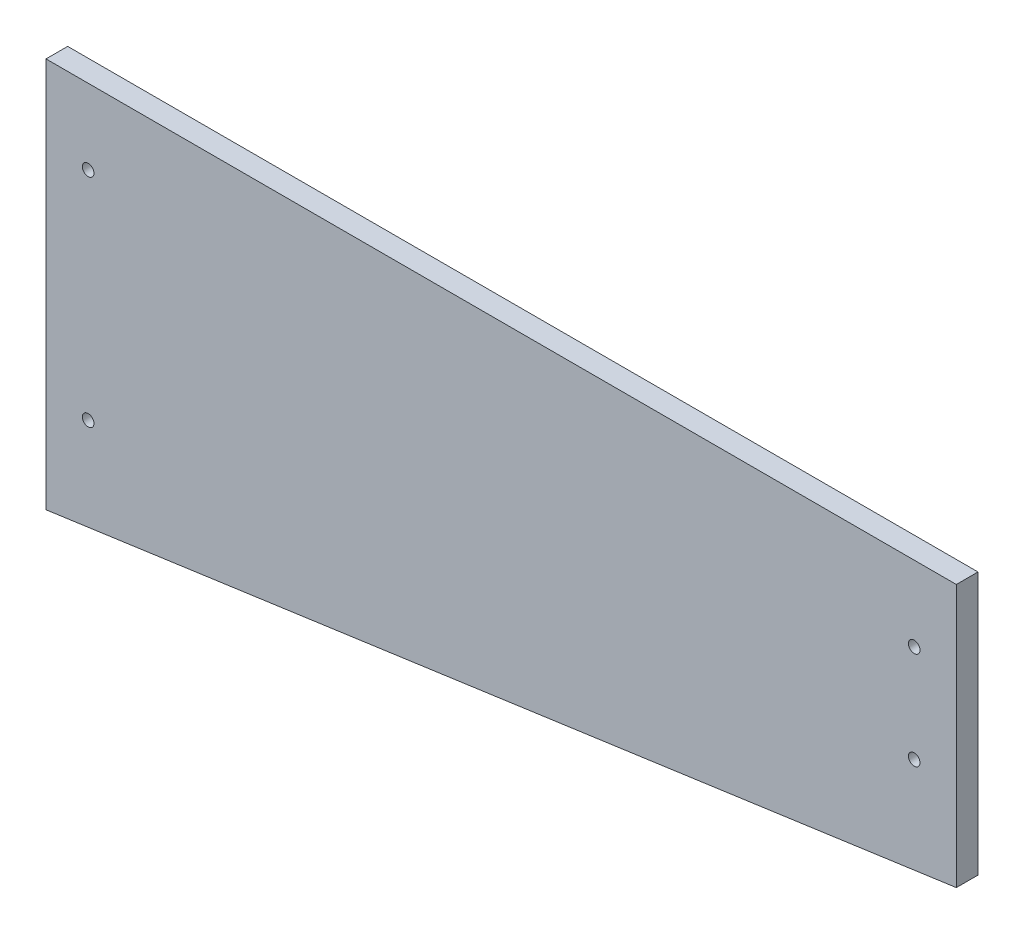
SolidWorks part; units mm, degrees
material "Acrylic (Medium-high impact)"
ref_plane "Front Plane" through (0, 0, 0) normal (0, 0, 1) x (1, 0, 0)
ref_plane "Top Plane" through (0, 0, 0) normal (0, 1, 0) x (1, 0, 0)
ref_plane "Right Plane" through (0, 0, 0) normal (1, 0, 0) x (0, 0, -1)
sketch "Sketch1" plane through (0, 0, 0) normal (0, 0, 1) x (1, 0, 0)
  line L1 (266.7, 114.4016) -> (0, 114.4016)
  line L2 (266.7, 114.4016) -> (266.7, 0)
  line L3 (266.7, 0) -> (0, 0)
  line L4 (0, 114.4016) -> (0, 0)
  line L5 (266.7, 114.4016) -> (0, 0) construction
  line L6 (266.7, 0) -> (0, 114.4016) construction
  point P0 (133.35, 57.2008)
  dimension "D1" = 114.4016
  dimension "D2" = 266.7
extrude "Boss-Extrude1" add sketch "Sketch1" along normal blind 6.35
hole_wizard "M3 Clearance Hole1" positions "Sketch2" profile "Sketch3" hole size "M3" standard "ANSI Metric" end condition through all
sketch "Sketch2" plane through (0, 0, 6.35) normal (0, 0, 1) x (1, 0, 0)
  line L0 (0, 114.4016) -> (0, 0) construction
  line L1 (266.7, 114.4016) -> (0, 114.4016) construction
  line L2 (266.7, 0) -> (266.7, 114.4016) construction
  point P0 (12.3444, 92.4052)
  point P2 (12.3444, 28.9052)
  point P4 (254.3556, 63.8302)
  point P6 (254.3556, 92.4052)
  dimension "D1" = 12.3444
  dimension "D2" = 21.9964
  dimension "D3" = 12.3444
  dimension "D4" = 63.5
  dimension "D5" = 28.575
sketch "Sketch3" plane through (12.3444, 92.4052, 6.35) normal (1, 0, 0) x (0, -1, 0)
  line L0 (0, 0) -> (0, 6.35)
  line L1 (0, 6.35) -> (1.7, 6.35)
  line L2 (1.7, 6.35) -> (1.7, 0)
  line L5 (1.7, 0) -> (0, 0)
  line L11 (0, -6.35) -> (0, 107.95) construction
  dimension "Thru Hole Dia." = 3.4
  dimension "Thru Hole Depth" = 6.35
sketch "Sketch4" plane through (0, 0, 6.35) normal (0, 0, 1) x (1, 0, 0)
  line L0 (0, 114.4016) -> (0, 0) construction
  line L1 (46.99, 95.3516) -> (50.4952, 95.3516)
  line L2 (46.99, 95.3516) -> (46.99, 19.1516)
  line L3 (46.99, 19.1516) -> (50.4952, 19.1516)
  line L4 (50.4952, 95.3516) -> (50.4952, 19.1516)
  line L5 (216.2048, 95.3516) -> (219.71, 95.3516)
  line L6 (216.2048, 95.3516) -> (216.2048, 19.1516)
  line L7 (216.2048, 19.1516) -> (219.71, 19.1516)
  line L8 (219.71, 95.3516) -> (219.71, 19.1516)
  line L9 (266.7, 0) -> (266.7, 114.4016) construction
  line L10 (266.7, 114.4016) -> (0, 114.4016) construction
  dimension "D1" = 3.5052
  dimension "D2" = 76.2
  dimension "D3" = 46.99
  dimension "D4" = 46.99
  dimension "D5" = 19.05
extrude "Cut-Extrude1" [suppressed] cut sketch "Sketch4" against normal through all
sketch "Sketch5" plane through (0, 0, 6.35) normal (0, 0, 1) x (1, 0, 0)
  line L0 (0, 0) -> (266.7, 0)
  line L1 (266.7, 0) -> (266.7, 37.4822)
  line L2 (266.7, 0) -> (266.7, 114.4016) construction
  line L3 (266.7, 37.4822) -> (0, 0)
  dimension "D1" = 8
extrude "Cut-Extrude2" cut sketch "Sketch5" against normal through all
